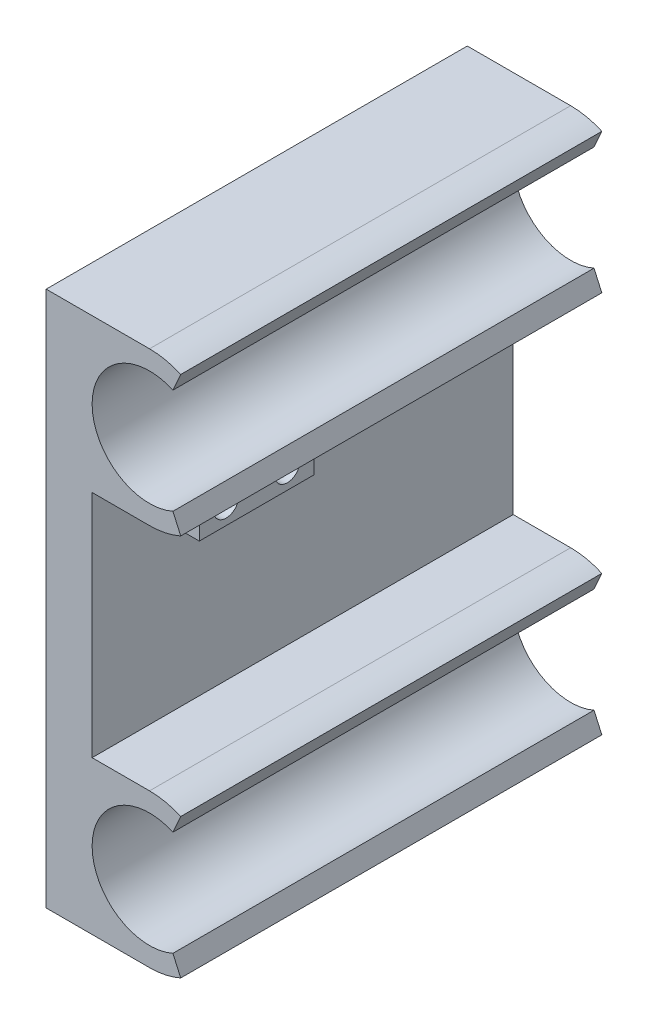
SolidWorks part; units mm, degrees
ref_plane "Plano frontal" through (0, 0, 0) normal (0, 0, 1) x (1, 0, 0)
ref_plane "Plano superior" through (0, 0, 0) normal (0, 1, 0) x (1, 0, 0)
ref_plane "Plano direito" through (0, 0, 0) normal (1, 0, 0) x (0, 0, -1)
sketch "Esboço1" plane through (0, 0, 0) normal (0, 0, 1) x (1, 0, 0)
  line L0 (0, 0) -> (67.7245, 0) construction
  line L1 (0, 35) -> (0, -35)
  line L2 (13.5, -25) -> (26.7005, -25) construction
  line L3 (16.5541, 18.15) -> (17.5721, 15.8667)
  line L4 (13.5, 15) -> (6, 15)
  line L5 (16.5541, -31.85) -> (17.5721, -34.1333)
  line L6 (6, -15) -> (6, 15)
  line L7 (13.5, -35) -> (0, -35)
  line L8 (13.5, 25) -> (26.7005, 25) construction
  line L9 (13.5, -15) -> (6, -15)
  line L10 (13.5, 35) -> (0, 35)
  line L11 (16.5541, -18.15) -> (17.5721, -15.8667)
  line L16 (16.5541, 31.85) -> (17.5721, 34.1333)
  arc A0 (16.5541, 31.85) -> (16.5541, 18.15) centre (13.5, 25) ccw
  arc A1 (17.5721, -34.1333) -> (13.5, -35) centre (13.5, -25) cw
  arc A2 (13.5, 15) -> (17.5721, 15.8667) centre (13.5, 25) ccw
  arc A3 (13.5, -15) -> (17.5721, -15.8667) centre (13.5, -25) cw
  arc A4 (16.5541, -31.85) -> (16.5541, -18.15) centre (13.5, -25) cw
  arc A5 (17.5721, 34.1333) -> (13.5, 35) centre (13.5, 25) ccw
  point P3 (0, 0)
  point P13 (13.5, 15)
  point P23 (6, -14.3834)
  point P24 (0, 0)
  dimension "D1" = 15
  dimension "D2" = 13.7
  dimension "D5" = 10
  dimension "D3" = 6
  dimension "D4" = 70
extrude "Ressalto-extrusão1" add sketch "Esboço1" along normal blind 55
sketch "Esboço3" plane through (6, 0, 0) normal (1, 0, 0) x (0, 0, -1)
  line L0 (-55, -15) -> (-55, 15) construction
  line L1 (-51, 12.5) -> (-36, 12.5)
  line L2 (-51, 12.5) -> (-51, 17.5)
  line L3 (-51, 17.5) -> (-36, 17.5)
  line L4 (-36, 12.5) -> (-36, 17.5)
  line L5 (-55, 17.5) -> (0, 17.5) construction
  line L6 (-55, 32.5) -> (-55, 17.5) construction
  line L7 (0, 17.5) -> (0, 32.5) construction
  line L8 (-55, 25) -> (0, 25) construction
  line L9 (0, 0) -> (-55, 0) construction
  line L10 (-27.5, 35) -> (-27.5, -35) construction
  line L11 (-55, 35) -> (0, 35) construction
  line L12 (-55, -35) -> (0, -35) construction
  line L13 (-43.5, 17.5) -> (-43.5, 12.5) construction
  circle A0 centre (-47.5, 15) radius 1.65
  circle A1 centre (-39.5, 15) radius 1.65
  point P27 (-51, 15)
  dimension "D5" = 3.3
  dimension "D1" = 7.5
  dimension "D2" = 8
  dimension "D3" = 40
  dimension "D4" = 15
  dimension "D6" = 30
extrude "Ressalto-extrusão2" add sketch "Esboço3" along normal blind 10
